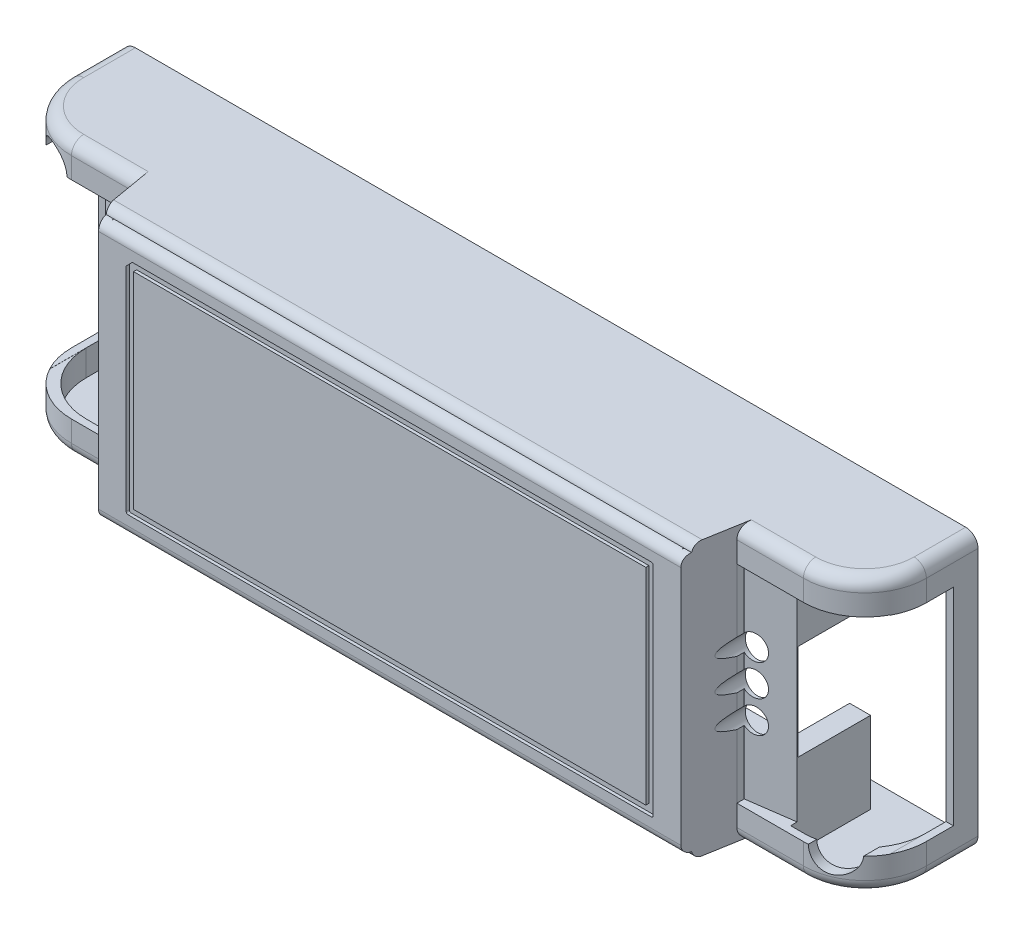
SolidWorks part; units mm, degrees
ref_plane "Front Plane" through (0, 0, 0) normal (0, 0, 1) x (1, 0, 0)
ref_plane "Top Plane" through (0, 0, 0) normal (0, 1, 0) x (1, 0, 0)
ref_plane "Right Plane" through (0, 0, 0) normal (1, 0, 0) x (0, 0, -1)
sketch "Sketch1" plane through (0, 0, 0) normal (0, 0, 1) x (1, 0, 0)
  line L1 (-34.7725, 22.265) -> (34.7725, 22.265)
  line L2 (-34.7725, 22.265) -> (-34.7725, -22.265)
  line L3 (-34.7725, -22.265) -> (34.7725, -22.265)
  line L4 (34.7725, 22.265) -> (34.7725, -22.265)
  line L5 (-34.7725, 22.265) -> (34.7725, -22.265) construction
  line L6 (-34.7725, -22.265) -> (34.7725, 22.265) construction
  point P0 (0, 0)
  dimension "D1" = 44.53
  dimension "D2" = 69.545
extrude "Boss-Extrude1" add sketch "Sketch1" along normal blind 26.17
sketch "Sketch2" plane through (0, 0, 26.17) normal (0, 0, 1) x (1, 0, 0)
  line L0 (-34.7725, -22.265) -> (34.7725, -22.265) construction
  line L1 (34.7725, 22.265) -> (13.9425, 22.265)
  line L2 (34.7725, 22.265) -> (34.7725, -22.265)
  line L3 (34.7725, -22.265) -> (13.9425, -22.265)
  line L4 (13.9425, 22.265) -> (13.9425, -22.265)
  dimension "D1" = 20.83
extrude "Cut-Extrude1" cut sketch "Sketch2" against normal blind 7.77
sketch "Sketch3" plane through (0, -22.265, 0) normal (0, -1, 0) x (1, 0, 0)
  line L0 (13.9425, 18.4) -> (13.9425, 26.17)
  line L1 (13.9425, 26.17) -> (12.5925, 26.17)
  line L2 (-34.7725, 26.17) -> (13.9425, 26.17) construction
  line L3 (12.5925, 26.17) -> (13.9425, 18.4)
  dimension "D1" = 22.18
extrude "Cut-Extrude2" cut sketch "Sketch3" against normal through all
sketch "Sketch4" plane through (0, 0, 18.4) normal (0, 0, 1) x (1, 0, 0)
  line L0 (13.9425, 22.265) -> (13.9425, -22.265) construction
  line L1 (63.8796, 16.865) -> (13.9425, 16.865)
  line L2 (63.8796, 16.865) -> (63.8796, -16.835)
  line L3 (63.8796, -16.835) -> (13.9425, -16.835)
  line L4 (13.9425, 16.865) -> (13.9425, -16.835)
  line L5 (34.7725, 22.265) -> (13.9425, 22.265) construction
  dimension "D1" = 33.7
  dimension "D2" = 0
  dimension "D3" = 5.4
extrude "Cut-Extrude3" cut sketch "Sketch4" against normal blind 1.2
sketch "Sketch5" plane through (0, 0, 18.4) normal (0, 0, 1) x (1, 0, 0)
  line L0 (13.9425, -16.835) -> (34.7725, -16.835) construction
  line L1 (33.5725, 16.865) -> (21.4925, 16.865)
  line L2 (33.5725, 16.865) -> (33.5725, -16.835)
  line L3 (33.5725, -16.835) -> (21.4925, -16.835)
  line L4 (21.4925, 16.865) -> (21.4925, -16.835)
  line L5 (34.7725, -22.265) -> (34.7725, -16.835) construction
  dimension "D1" = 33.7
  dimension "D2" = 12.08
  dimension "D3" = 1.2
extrude "Cut-Extrude4" cut sketch "Sketch5" against normal through all
sketch "Sketch6" plane through (34.7725, 0, 0) normal (1, 0, 0) x (0, 0, -1)
  line L0 (0, -22.265) -> (0, 22.265) construction
  line L1 (-10.22, -16.815) -> (-4, -16.815)
  line L2 (-10.22, -16.815) -> (-10.22, 16.815)
  line L3 (-10.22, 16.815) -> (-4, 16.815)
  line L4 (-4, -16.815) -> (-4, 16.815)
  line L5 (-18.4, 22.265) -> (0, 22.265) construction
  line L6 (-18.4, -22.265) -> (0, -22.265) construction
  dimension "D1" = 4
  dimension "D2" = 6.22
  dimension "D3" = 5.45
  dimension "D4" = 5.45
extrude "Cut-Extrude5" cut sketch "Sketch6" against normal blind 1.2
sketch "Sketch8" plane through (34.7725, 0, 0) normal (1, 0, 0) x (0, 0, -1)
  line L0 (-18.4, -22.265) -> (-18.4, -16.835) construction
  line L1 (-10.22, -16.815) -> (-18.4, -16.815)
  line L2 (-10.22, -16.815) -> (-10.22, 16.815)
  line L3 (-10.22, 16.815) -> (-18.4, 16.815)
  line L4 (-18.4, -16.815) -> (-18.4, 16.815)
extrude "Cut-Extrude6" cut sketch "Sketch8" against normal blind 1.2
sketch "Sketch9" plane through (21.4925, 0, 0) normal (1, 0, 0) x (0, 0, -1)
  line L0 (0, 16.865) -> (-17.2, 16.865) construction
  line L1 (0, -16.835) -> (-4.2, -16.835)
  line L2 (0, -16.835) -> (0, 16.865)
  line L3 (0, 16.865) -> (-4.2, 16.865)
  line L4 (-4.2, -16.835) -> (-4.2, 16.865)
  dimension "D1" = 4.2
extrude "Cut-Extrude7" cut sketch "Sketch9" against normal blind 5
sketch "Sketch11" plane through (21.4925, 0, 0) normal (1, 0, 0) x (0, 0, -1)
  line L0 (-4.2, 16.865) -> (-4.2, -16.835) construction
  line L1 (-16, -7.785) -> (-4.2, -7.785)
  line L2 (-16, -7.785) -> (-16, 7.815)
  line L3 (-16, 7.815) -> (-4.2, 7.815)
  line L4 (-4.2, -7.785) -> (-4.2, 7.815)
  line L5 (-17.2, -16.835) -> (-17.2, 16.865) construction
  line L6 (-4.2, -16.835) -> (-17.2, -16.835) construction
  dimension "D1" = 15.6
  dimension "D2" = 1.2
  dimension "D3" = 9.05
extrude "Cut-Extrude8" cut sketch "Sketch11" against normal blind 5
sketch "Sketch13" plane through (0, 16.865, 0) normal (0, -1, 0) x (1, 0, 0)
  line L0 (33.5725, 17.2) -> (21.4925, 17.2)
  line L1 (21.4925, 4.2) -> (21.4925, 17.2) construction
  line L2 (21.4925, 17.2) -> (21.4925, 4.2)
  line L3 (21.4925, 4.2) -> (16.4925, 4.2)
  line L4 (16.4925, 0) -> (16.4925, 4.2) construction
  line L5 (16.4925, 4.2) -> (21.4925, 4.2) construction
  line L6 (16.4925, 4.2) -> (16.4925, 0)
  line L7 (16.4925, 0) -> (33.5725, 0)
  line L8 (33.5725, 0) -> (33.5725, 17.2)
extrude "Cut-Extrude9" cut sketch "Sketch13" against normal blind 4.2
sketch "Sketch14" plane through (0, -16.835, 0) normal (0, 1, 0) x (1, 0, 0)
  line L0 (33.5725, -17.2) -> (21.4925, -17.2)
  line L1 (21.4925, -17.2) -> (21.4925, -4.2)
  line L2 (21.4925, -4.2) -> (16.4925, -4.2)
  line L3 (16.4925, -4.2) -> (16.4925, 0)
  line L4 (16.4925, 0) -> (33.5725, 0)
  line L5 (33.5725, 0) -> (33.5725, -17.2)
extrude "Cut-Extrude10" cut sketch "Sketch14" against normal blind 4.2
shell "Shell3" thickness 1.2
sketch "Sketch15" plane through (-34.7725, 0, 0) normal (-1, 0, 0) x (0, 0, 1)
  line L0 (26.17, 22.265) -> (0, 22.265) construction
  line L1 (24.97, 21.065) -> (0, 21.065)
  line L2 (24.97, 21.065) -> (24.97, -21.065)
  line L3 (24.97, -21.065) -> (0, -21.065)
  line L4 (0, 21.065) -> (0, -21.065)
  line L5 (26.17, 22.265) -> (26.17, -22.265) construction
  dimension "D1" = 1.2
  dimension "D2" = 1.2
extrude "Cut-Extrude11" cut sketch "Sketch15" against normal blind 4.2
sketch "Sketch16" plane through (16.4925, 0, 0) normal (1, 0, 0) x (0, 0, -1)
  line L0 (-16, -7.785) -> (-4.2, -7.785)
  line L1 (-4.2, -7.785) -> (-4.2, -21.035)
  line L2 (-4.2, -21.035) -> (0, -21.035)
  line L3 (0, -21.035) -> (0, 21.065)
  line L4 (0, 21.065) -> (-4.2, 21.065)
  line L5 (-4.2, 21.065) -> (-4.2, 7.815)
  line L6 (-4.2, 7.815) -> (-16, 7.815)
  line L7 (-16, 7.815) -> (-16, -7.785)
extrude "Cut-Extrude12" cut sketch "Sketch16" against normal blind 4.2
sketch "Sketch18" plane through (0, 0, 4.2) normal (0, 0, -1) x (-1, 0, 0)
  line L0 (-21.4925, 21.065) -> (-15.2925, 21.065) construction
  line L1 (-20.2925, 21.065) -> (-15.2925, 21.065)
  line L2 (-20.2925, 21.065) -> (-20.2925, 9.015)
  line L3 (-20.2925, 9.015) -> (-15.2925, 9.015)
  line L4 (-15.2925, 21.065) -> (-15.2925, 9.015)
  line L5 (-15.2925, 21.065) -> (-15.2925, 7.815) construction
  line L6 (-33.5725, -21.035) -> (-15.2925, -21.035) construction
  line L7 (-20.2925, -21.035) -> (-15.2925, -21.035)
  line L8 (-20.2925, -21.035) -> (-20.2925, -8.985)
  line L9 (-20.2925, -8.985) -> (-15.2925, -8.985)
  line L10 (-15.2925, -21.035) -> (-15.2925, -8.985)
  line L11 (-15.2925, -7.785) -> (-15.2925, -21.035) construction
  line L12 (-15.2925, -7.785) -> (-21.4925, -7.785) construction
  line L13 (-15.2925, 7.815) -> (-21.4925, 7.815) construction
  line L14 (-21.4925, -7.785) -> (-21.4925, -21.035) construction
  line L15 (-21.4925, 21.065) -> (-21.4925, 16.865) construction
  dimension "D1" = 1.2
  dimension "D2" = 1.2
  dimension "D3" = 1.2
  dimension "D4" = 1.2
extrude "Cut-Extrude13" cut sketch "Sketch18" against normal blind 4.2
sketch "Sketch19" plane through (0, 0, 24.97) normal (0, 0, -1) x (-1, 0, 0)
  line L0 (-11.583, 21.065) -> (-11.583, -21.065) construction
  line L1 (34.7725, -21.065) -> (-11.583, -21.065)
  line L2 (34.7725, -21.065) -> (34.7725, -19.565)
  line L3 (34.7725, -19.565) -> (-11.583, -19.565)
  line L4 (-11.583, -21.065) -> (-11.583, -19.565)
  line L5 (34.7725, -21.065) -> (34.7725, 21.065) construction
  line L6 (-11.583, 21.065) -> (34.7725, 21.065)
  line L7 (-11.583, 21.065) -> (-11.583, 19.565)
  line L8 (-11.583, 19.565) -> (34.7725, 19.565)
  line L9 (34.7725, 21.065) -> (34.7725, 19.565)
  dimension "D1" = 1.5
  dimension "D2" = 1.5
extrude "Boss-Extrude2" add sketch "Sketch19" along normal blind 2.5
sketch "Sketch22" plane through (0, 0, 26.17) normal (0, 0, 1) x (1, 0, 0)
  line L1 (12.5925, -22.265) -> (-37.0858, -22.265)
  line L2 (12.5925, -22.265) -> (12.5925, -21.065)
  line L3 (12.5925, -21.065) -> (-37.0858, -21.065)
  line L4 (-37.0858, -22.265) -> (-37.0858, -21.065)
  dimension "D1" = 1.2
extrude "Cut-Extrude16" cut sketch "Sketch22" against normal blind 1.5
sketch "Sketch23" plane through (12.5925, 0, 0) normal (-1, 0, 0) x (0, 0, 1)
  line L1 (24.67, -21.065) -> (26.17, -21.065)
  line L2 (24.67, -21.065) -> (24.67, -22.265)
  line L3 (24.67, -22.265) -> (26.17, -22.265)
  line L4 (26.17, -21.065) -> (26.17, -22.265)
extrude "Cut-Extrude17" cut sketch "Sketch23" against normal blind 1.5
sketch "Sketch24" plane through (0, 0, 26.17) normal (0, 0, 1) x (1, 0, 0)
  line L0 (12.5925, 22.265) -> (12.5925, -21.065) construction
  line L1 (-34.7725, 22.265) -> (12.5925, 22.265)
  line L2 (-34.7725, 22.265) -> (-34.7725, 21.065)
  line L3 (-34.7725, 21.065) -> (12.5925, 21.065)
  line L4 (12.5925, 22.265) -> (12.5925, 21.065)
  dimension "D1" = 1.2
extrude "Cut-Extrude18" cut sketch "Sketch24" against normal blind 1.5
sketch "Sketch25" plane through (12.5925, 0, 0) normal (-1, 0, 0) x (0, 0, 1)
  line L1 (24.67, 22.265) -> (26.17, 22.265)
  line L2 (24.67, 22.265) -> (24.67, 21.065)
  line L3 (24.67, 21.065) -> (26.17, 21.065)
  line L4 (26.17, 22.265) -> (26.17, 21.065)
extrude "Cut-Extrude19" cut sketch "Sketch25" against normal blind 1.5
sketch "Sketch26" plane through (0, 0, 26.17) normal (0, 0, 1) x (1, 0, 0)
  line L0 (-34.7725, 21.065) -> (11.583, 21.065) construction
  line L1 (8.0925, 17.9519) -> (-34.7725, 17.9519)
  line L2 (8.0925, 17.9519) -> (8.0925, -17.955)
  line L3 (8.0925, -17.955) -> (-34.7725, -17.955)
  line L4 (-34.7725, 17.9519) -> (-34.7725, -17.955)
  line L5 (12.5925, 21.065) -> (12.5925, -21.065) construction
  line L6 (-34.7725, 21.065) -> (-34.7725, -21.065) construction
  line L7 (12.5925, -21.065) -> (-34.7725, -21.065) construction
  line L9 (-34.7725, 16.7519) -> (6.8925, 16.7519)
  line L10 (-34.7725, 16.7519) -> (-34.7725, -16.755)
  line L11 (-34.7725, -16.755) -> (6.8925, -16.755)
  line L12 (6.8925, 16.7519) -> (6.8925, -16.755)
  line M9 (-34.7725, 21.065) -> (-34.7725, -21.065)
  dimension "D1" = 3.1131
  dimension "D2" = 4.5
  dimension "D3" = 0
  dimension "D4" = 3.11
  dimension "D5" = 1.2
  dimension "D6" = 1.2
  dimension "D7" = 1.2
extrude "Cut-Extrude20" cut sketch "Sketch26" against normal blind 0.5 contours L9 L12 L11 L3 L2 L1 M9
fillet "Fillet1" radius 1.5 4 edges at (-11.09, 21.065, 26.17) (-10.9597, 22.265, 24.67) (-11.09, -21.065, 26.17) (-10.9597, -22.265, 24.67)
fillet "Fillet5" radius 10 2 edges at (33.5725, 18.965, 17.2) (33.5725, -18.935, 17.2)
fillet "Fillet6" radius 10 2 edges at (34.7725, -19.55, 18.4) (34.7725, 19.565, 18.4)
fillet "Fillet7" radius 2 6 edges at (19.3575, 22.265, 18.4) (31.8436, 22.265, 15.4711) (19.3575, -22.265, 18.4) (31.8436, -22.265, 15.4711) (34.7725, 22.265, 4.2) (34.7725, -22.265, 4.2)
mirror "Mirror1" about plane through (-34.7725, 22.265, 26.17) normal (1, 0, 0) of bodies 122
sketch "Sketch27" plane through (0, 0, 4.2) normal (0, 0, -1) x (-1, 0, 0)
  line L1 (89.8375, 9.015) -> (84.8375, 9.015) construction
  line L2 (84.8375, 7.815) -> (87.8509, 7.815)
  line L3 (84.8375, 7.815) -> (84.8375, 9.015)
  line L4 (84.8375, 9.015) -> (87.8509, 9.015)
  line L5 (87.8509, 7.815) -> (87.8509, 9.015)
  line L6 (84.8375, -7.785) -> (91.0375, -7.785) construction
  line L7 (84.8375, -8.985) -> (87.8509, -8.985)
  line L8 (84.8375, -8.985) -> (84.8375, -7.785)
  line L9 (84.8375, -7.785) -> (87.8509, -7.785)
  line L10 (87.8509, -8.985) -> (87.8509, -7.785)
extrude "Cut-Extrude21" cut sketch "Sketch27" against normal up to surface (11.8 mm away) up to face at (-87.1125, 0.015, 16)
sketch "Sketch28" plane through (0, 0, 4.2) normal (0, 0, -1) x (-1, 0, 0)
  line L0 (-15.2925, -8.985) -> (-20.2925, -8.985) construction
  line L1 (-15.2925, -7.785) -> (-18.0902, -7.785)
  line L2 (-15.2925, -7.785) -> (-15.2925, -8.985)
  line L3 (-15.2925, -8.985) -> (-18.0902, -8.985)
  line L4 (-18.0902, -7.785) -> (-18.0902, -8.985)
  line L5 (-15.2925, 7.815) -> (-21.4925, 7.815) construction
  line L6 (-15.2925, 9.015) -> (-18.0902, 9.015)
  line L7 (-15.2925, 9.015) -> (-15.2925, 7.815)
  line L8 (-15.2925, 7.815) -> (-18.0902, 7.815)
  line L9 (-18.0902, 9.015) -> (-18.0902, 7.815)
extrude "Cut-Extrude22" cut sketch "Sketch28" against normal up to surface (11.8 mm away) up to face at (17.5675, 0.015, 16)
sketch "Sketch29" plane through (0, 0, 16) normal (0, 0, -1) x (-1, 0, 0)
  line L0 (-12.7425, 18.065) -> (-12.7425, -18.035) construction
  line L1 (-18.0902, -7.785) -> (-12.7425, -7.785)
  line L2 (-18.0902, -7.785) -> (-18.0902, 7.8605)
  line L3 (-18.0902, 7.8605) -> (-12.7425, 7.8605)
  line L4 (-12.7425, -7.785) -> (-12.7425, 7.8605)
extrude "Cut-Extrude23" cut sketch "Sketch29" against normal blind 0.5
sketch "Sketch30" plane through (0, 0, 16.5) normal (0, 0, -1) x (-1, 0, 0)
  line L0 (-12.7425, -7.785) -> (-12.7425, 7.8605) construction
  line L1 (-12.7425, 18.065) -> (-12.7425, -18.035) construction
  line L3 (-18.0902, -7.785) -> (-12.7425, -7.785) construction
  line L4 (-12.7425, 7.8605) -> (-18.0902, 7.8605) construction
  circle A0 centre (-15.4125, -5.115) radius 2
  circle A1 centre (-15.4125, 0.0605) radius 2
  circle A2 centre (-15.4125, 5.1905) radius 2
  dimension "D1" = 2.67
  dimension "D2" = 2.67
  dimension "D3" = 2.67
  dimension "D7" = 4
  dimension "D8" = 4
  dimension "D9" = 4
  dimension "D4" = 2.67
  dimension "D5" = 2.67
  dimension "D6" = 7.8
extrude "Cut-Extrude24" cut sketch "Sketch30" against normal through all
sketch "Sketch31" plane through (0, 0, 16) normal (0, 0, -1) x (-1, 0, 0)
  line L0 (82.2875, 18.065) -> (82.2875, -18.035) construction
  line L1 (87.8509, -7.785) -> (82.2875, -7.785)
  line L2 (87.8509, -7.785) -> (87.8509, 7.8686)
  line L3 (87.8509, 7.8686) -> (82.2875, 7.8686)
  line L4 (82.2875, -7.785) -> (82.2875, 7.8686)
extrude "Cut-Extrude25" cut sketch "Sketch31" against normal blind 0.5
sketch "Sketch32" plane through (0, 0, 16.5) normal (0, 0, -1) x (-1, 0, 0)
  line L1 (87.8509, 7.8686) -> (82.2875, 7.8686) construction
  circle A0 centre (84.9902, -4.5968) radius 2
  circle A1 centre (84.9902, 4.7486) radius 2
  dimension "D1" = 4
  dimension "D2" = 4
  dimension "D3" = 9.3454
  dimension "D4" = 3.12
extrude "Cut-Extrude26" cut sketch "Sketch32" against normal through all
chamfer "Chamfer2" distance 1 angle 45 1 edges at (-77.6375, 17.9519, 25.92)
fillet "Fillet8" radius 0.3 3 edges at (-77.6375, -17.955, 25.92) (8.0925, -17.955, 25.92) (8.0925, 17.9519, 25.92)
sketch "Sketch33" plane through (0, 0, 18.4) normal (0, 0, 1) x (1, 0, 0)
  line L0 (-103.1175, 16.865) -> (-94.3175, 16.865) construction
  line L1 (-83.4875, 20.265) -> (-83.4875, 16.865) construction
  circle A0 centre (-98.1775, 16.865) radius 3.09
  dimension "D1" = 6.18
  dimension "D2" = 14.69
extrude "Cut-Extrude27" cut sketch "Sketch33" against normal through all
sketch "Sketch34" plane through (0, 0, 18.4) normal (0, 0, 1) x (1, 0, 0)
  line L0 (33.5725, -16.835) -> (24.7725, -16.835) construction
  line L1 (13.9425, -16.835) -> (13.9425, -20.265) construction
  circle A0 centre (28.6325, -16.835) radius 3.09
  dimension "D2" = 6.18
  dimension "D1" = 14.69
extrude "Cut-Extrude28" cut sketch "Sketch34" against normal through all
chamfer "Chamfer5" distance 7.5 angle 8 1 edges at (21.4925, 0.015, 17.2)
chamfer "Chamfer6" distance 7.5 angle 8 1 edges at (-91.0375, 0.015, 17.2)
sketch "Sketch35" plane through (0, 21.065, 0) normal (0, -1, 0) x (1, 0, 0)
  line L0 (-103.1175, 0) -> (33.5725, 0) construction
  line L1 (5.0925, 3) -> (-1.4075, 3)
  line L2 (5.0925, 3) -> (5.0925, 5)
  line L3 (5.0925, 5) -> (-1.4075, 5)
  line L4 (-1.4075, 3) -> (-1.4075, 5)
  line L5 (33.5725, 0) -> (33.5725, 7.2) construction
  line L6 (-103.1175, 0) -> (-103.1175, 7.2) construction
  line L7 (-74.7575, 5) -> (-68.2575, 5)
  line L8 (-74.7575, 5) -> (-74.7575, 3)
  line L9 (-74.7575, 3) -> (-68.2575, 3)
  line L10 (-68.2575, 5) -> (-68.2575, 3)
  dimension "D1" = 6.5
  dimension "D2" = 3
  dimension "D3" = 2
  dimension "D4" = 28.48
  dimension "D5" = 6.5
  dimension "D6" = 2
  dimension "D7" = 28.36
extrude "Cut-Extrude29" cut sketch "Sketch35" against normal blind 0.5
chamfer "Chamfer7" distance 0.5 angle 45 2 edges at (-71.5075, 21.065, 5) (1.8425, 21.065, 5)
mirror "Mirror4" about plane through (0, 0, 0) normal (0, 1, 0) of "Cut-Extrude29"
chamfer "Chamfer8" distance 0.5 angle 45 2 edges at (-71.5075, -21.065, 5) (1.8425, -21.065, 5)
